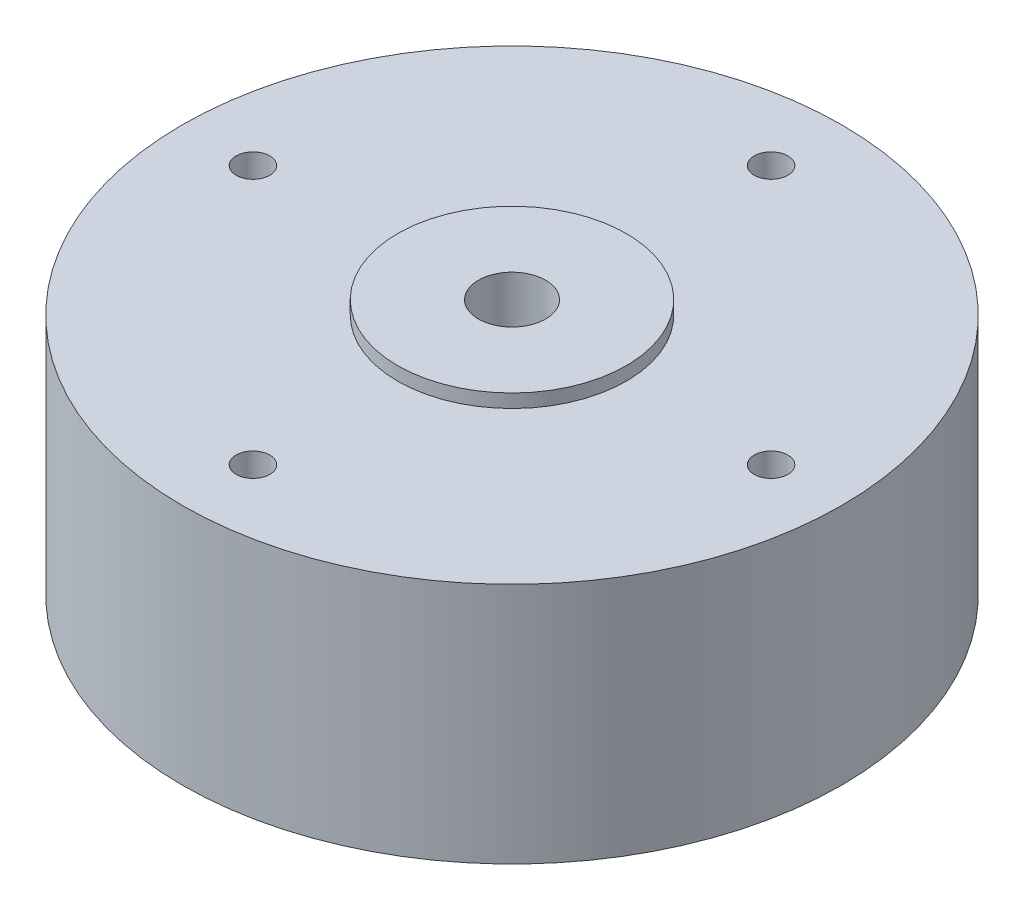
SolidWorks part; units mm, degrees
ref_plane "Front plane" through (0, 0, 0) normal (0, 0, 1) x (1, 0, 0)
ref_plane "Top plane" through (0, 0, 0) normal (0, 1, 0) x (1, 0, 0)
ref_plane "Right plane" through (0, 0, 0) normal (1, 0, 0) x (0, 0, -1)
ref_axis "Axis X" through (0, 0, 0) along (1, 0, 0)
ref_axis "Axis Y" through (0, 0, 0) along (0, 1, 0)
ref_axis "Axis Z" through (0, 0, 0) along (0, 0, 1)
sketch "Sketch1" plane through (0, 0, 0) normal (0, 1, 0) x (1, 0, 0)
  circle A0 centre (0, 0) radius 24.5
  dimension "D1" = 49
extrude "Extrude1" add sketch "Sketch1" along normal blind 19
sketch "Sketch2" plane through (0, 19, 0) normal (0, 1, 0) x (1, 0, 0)
  circle A0 centre (0, 0) radius 8.5
  circle A1 centre (0, 0) radius 24.5
  dimension "D1" = 49
  dimension "D2" = 17
extrude "Extrude2" cut sketch "Sketch2" against normal blind 1
sketch "Sketch3" plane through (0, 19, 0) normal (0, 1, 0) x (1, 0, 0)
  line L0 (0, 0) -> (0, 19.25) construction
  circle A0 centre (0, 0) radius 19.25 construction
  circle A1 centre (0, 19.25) radius 1.25
  circle A2 centre (19.25, 0) radius 1.25
  circle A3 centre (0, -19.25) radius 1.25
  circle A4 centre (-19.25, 0) radius 1.25
  dimension "D1" = 38.5
  dimension "D2" = 2.5
extrude "Extrude3" cut sketch "Sketch3" against normal blind 4
sketch "Sketch4" plane through (0, 0, 0) normal (0, -1, 0) x (1, 0, 0)
  line L0 (0, 0) -> (0, 12.5) construction
  circle A0 centre (0, 0) radius 12.5 construction
  circle A1 centre (0, 12.5) radius 1.5
  circle A2 centre (12.5, 0) radius 1.5
  circle A3 centre (0, -12.5) radius 1.5
  circle A4 centre (-12.5, 0) radius 1.5
  dimension "D1" = 3
  dimension "D3" = 25
  dimension "D2" = 4
extrude "Extrude4" cut sketch "Sketch4" against normal blind 3
chamfer "Chamfer1" [suppressed] distance 0.5 angle 45
sketch "Sketch6" plane through (0, 0, 0) normal (0, -1, 0) x (1, 0, 0)
  circle A0 centre (0, 0) radius 2.5
  dimension "D1" = 5
extrude "Extrude6" cut sketch "Sketch6" against normal through all
equation "\"motor_D\"= 49'Motor diameter"
equation "\"motor_H\"= 19'Motor heigh"
equation "\"motor_d1\"= 38.5'Seating diameter of screws on the fixed part of the motor"
equation "\"motor_s1\"= 2.5'Screws diameter on the fixed part of motor"
equation "\"motor_d2\"= 25'Seating diameter of screws on the moving part of the motor (if this parameter is not determine, write 0)"
equation "\"motor_s2\"= 3'Screws diameter on the moving part of motor"
equation "\"motor_Dc\"= 5'Central hole diameter of motor"
equation "\"bearing_d1\"= 8'Bearing inner diameter"
equation "\"bearing_d2\"= 16'Bearing external diameter"
equation "\"bearing h\"= 5'Bearing heigh"
equation "\"pin_d\"= 2'Pin diameter"
equation "\"pin_h\"= 13'Pin heigh"
equation "\"magnet_d1\"= 5'Magnet inner diameter"
equation "\"magnet_d2\"= 9.5'Magnet external diameter"
equation "\"magnet_h\"= 3'Magnet heigh"
equation "\"motor_a2\"= 0'Seating parameter in rectangle of screws on the moving part of the motor"
equation "\"motor_b2\"= 0'Seating parameter in rectangle of screws on the moving part of the motor"
equation "\"D1@Sketch1\"=\"motor_D\""
equation "\"D1@Extrude1\"=\"motor_H\""
equation "\"D1@Sketch2\"=\"motor_D\""
equation "\"motor_cmd\"= 17'Central magnet mount diameter"
equation "\"motor_cmh\"= 1'Central magnet mount heigh (if not write 0)"
equation "\"D2@Sketch2\"=\"motor_cmd\""
equation "\"D1@Extrude2\"= \"motor_cmh\""
equation "\"Extrude2\"= IIF ( \"motor_cmh\" = 0 , \"suppressed\" , \"unsuppressed\" )"
equation "\"D1@Sketch3\"=\"motor_d1\""
equation "\"D2@Sketch3\"=\"motor_s1\""
equation "\"D1@Extrude3\"=\"motor_cmh\"+3"
equation "\"D1@Sketch4\"=\"motor_s2\""
equation "\"D3@Sketch4\"=if( \"motor_d2\"=0,10,\"motor_d2\")"
equation "\"Extrude4\"= IIF ( \"motor_d2\" = 0 , \"suppressed\" , \"unsuppressed\" )"
equation "\"Extrude5\"= IIF ( \"motor_d2\" = 0 , \"unsuppressed\" , \"suppressed\" )"
equation "\"D1@Sketch6\"=\"motor_Dc\""
equation "\"motor_whR\"= 17'Distance from center of motor to wires"
equation "\"print_offset\"= 0.2'Offset for printing holes"
equation "\"ft_sensor_d1\"= 9.8"
equation "\"ft_sensor_d2\"= 24.9"
equation "\"ft_sensor_d3\"= 22.6'Inner diameter of "
equation "\"ft_sensor_h\"= 7.1"
equation "\"ft_sensor_whD\" = 5"
